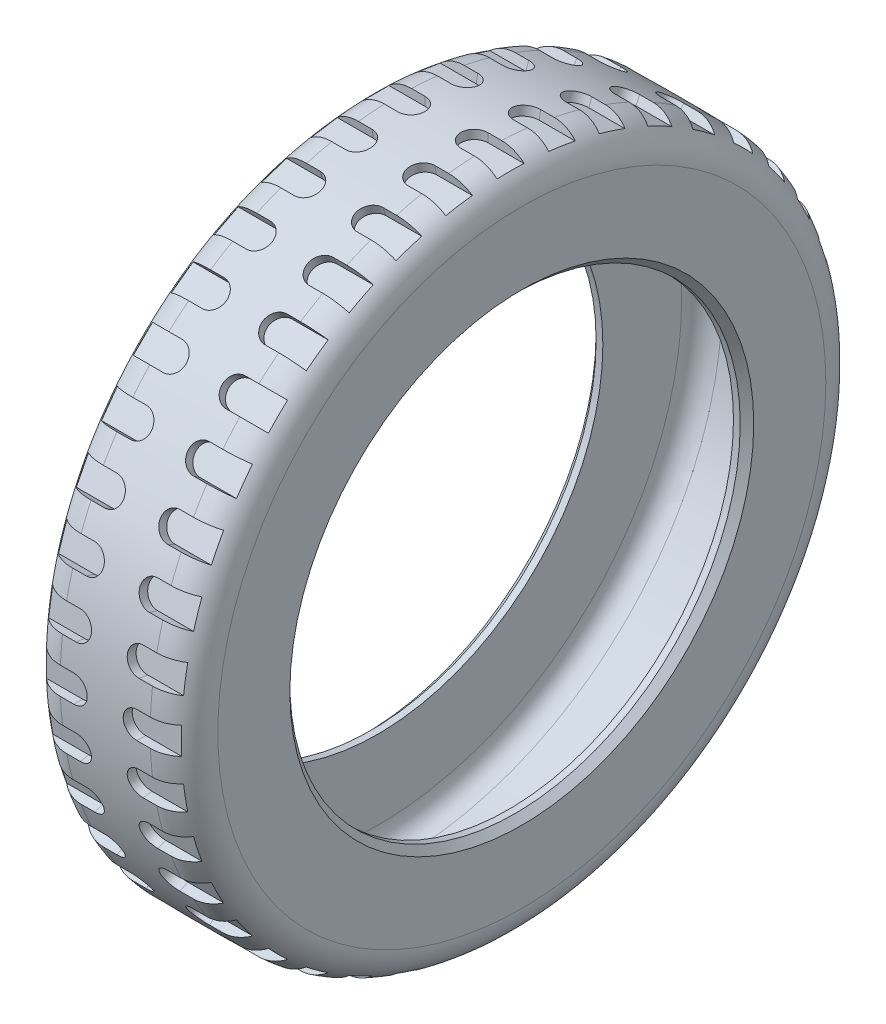
SolidWorks part; units mm, degrees
ref_plane "Front Plane" through (0, 0, 0) normal (0, 0, 1) x (1, 0, 0)
ref_plane "Top Plane" through (0, 0, 0) normal (0, 1, 0) x (1, 0, 0)
ref_plane "Right Plane" through (0, 0, 0) normal (1, 0, 0) x (0, 0, -1)
sketch "Sketch1" plane through (0, 0, 0) normal (0, 0, 1) x (1, 0, 0)
  line L0 (0, 67.4855) -> (0, 0) construction
  line L1 (0, 0) -> (-67.2383, 0) construction
  line L2 (-17.5, 50) -> (-17.5, 67.5)
  line L3 (-10, 75) -> (10, 75)
  line L4 (17.5, 67.5) -> (17.5, 50)
  line L5 (-14.5, 50) -> (-14.5, 67.5)
  line L6 (-10, 72) -> (10, 72)
  line L7 (14.5, 67.5) -> (14.5, 50)
  line L8 (-17.5, 50) -> (-14.5, 50)
  line L9 (14.5, 50) -> (17.5, 50)
  arc A0 (10, 75) -> (17.5, 67.5) centre (10, 67.5) cw
  arc A1 (-17.5, 67.5) -> (-10, 75) centre (-10, 67.5) cw
  arc A2 (-14.5, 67.5) -> (-10, 72) centre (-10, 67.5) cw
  arc A3 (10, 72) -> (14.5, 67.5) centre (10, 67.5) cw
  dimension "D4" = 7.5
  dimension "D1" = 50
  dimension "D2" = 75
  dimension "D3" = 35
  dimension "D5" = 3
revolve "Revolve1" add sketch "Sketch1" angle 360 about L1
chamfer "Chamfer1" distance 1.5 angle 45 2 edges at (-17.5, 0, -50) (17.5, 0, -50)
ref_plane "Plane1" through (0, 75, 0) normal (0, 1, 0) x (1, 0, 0)
sketch "Sketch2" plane through (0, 75, 0) normal (0, 1, 0) x (1, 0, 0)
  line L0 (0, 0) -> (17.5, 0) construction
  line L1 (17.5, -67.5) -> (17.5, 67.5) construction
  line L3 (7, 3) -> (15, 3)
  line L5 (7, -3) -> (15, -3)
  line L6 (15, 3) -> (15, -3)
  arc A0 (7, 3) -> (7, -3) centre (7, 0) ccw
  dimension "D3" = 3
  dimension "D1" = 7
  dimension "D2" = 2.5
extrude "Cut-Extrude6" cut sketch "Sketch2" against normal blind 2 contours L3 L6 L5 A0
pattern_circular "CirPattern1" count 40 over 360 about axis through (14.5, 0, 0) along (1, 0, 0) of "Cut-Extrude6"
mirror "Mirror1" about plane through (0, 0, 0) normal (1, 0, 0) of "CirPattern1"
